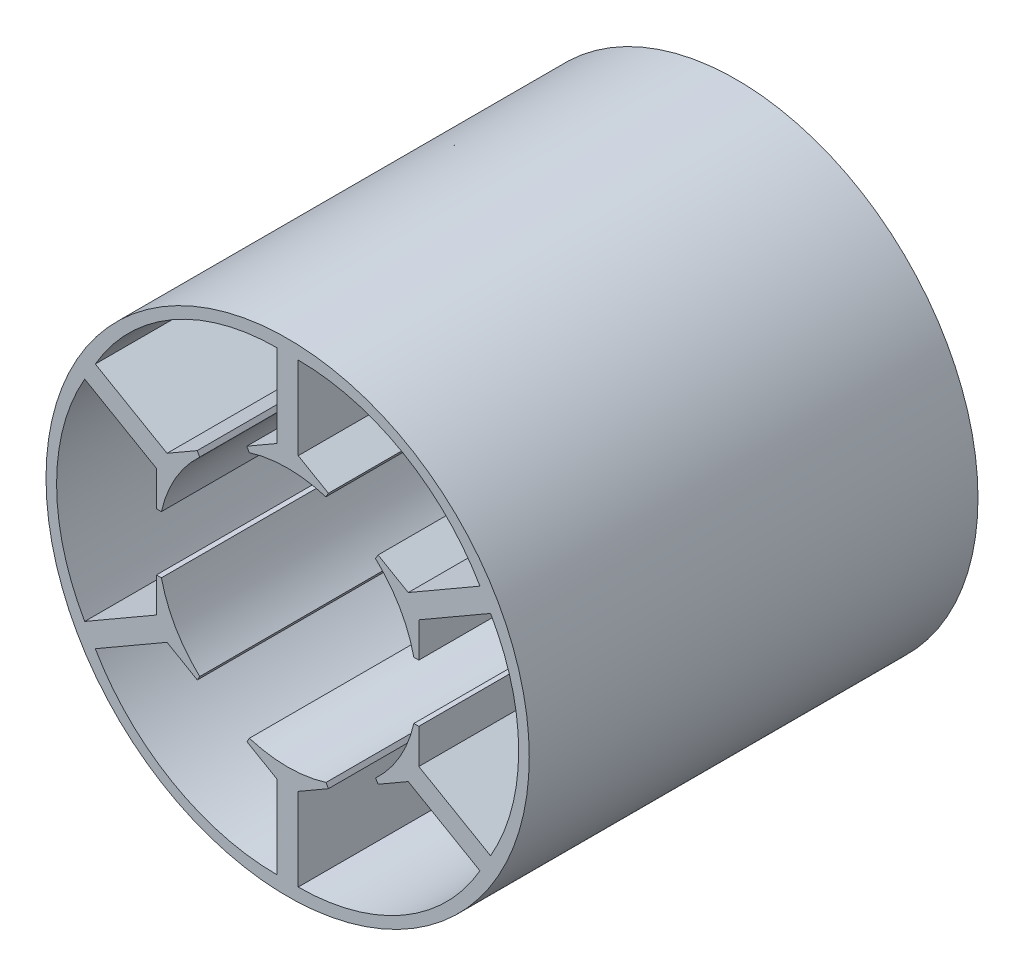
SolidWorks part; units mm, degrees
ref_plane "Front Plane" through (0, 0, 0) normal (0, 0, 1) x (1, 0, 0)
ref_plane "Top Plane" through (0, 0, 0) normal (0, 1, 0) x (1, 0, 0)
ref_plane "Right Plane" through (0, 0, 0) normal (1, 0, 0) x (0, 0, -1)
sketch "Motor_Base" plane through (0, 0, 0) normal (0, 0, 1) x (1, 0, 0)
  line L0 (0, 0) -> (0, 37.1463) construction
  line L1 (1.5331, 21.0694) -> (1.5331, 33.0694)
  line L2 (-1.5331, 21.0694) -> (-1.5331, 33.0694)
  line L3 (17.468, 11.8694) -> (27.8603, 17.8694)
  line L4 (19.0011, 9.214) -> (29.3934, 15.214)
  line L5 (19.0011, -9.186) -> (29.3934, -15.186)
  line L6 (17.468, -11.8414) -> (27.8603, -17.8414)
  line L7 (1.5331, -21.0414) -> (1.5331, -33.0414)
  line L8 (-1.5331, -21.0414) -> (-1.5331, -33.0414)
  line L9 (-17.468, -11.8414) -> (-27.8603, -17.8414)
  line L10 (-19.0011, -9.186) -> (-29.3934, -15.186)
  line L11 (-19.0011, 9.214) -> (-29.3934, 15.214)
  line L12 (-17.468, 11.8694) -> (-27.8603, 17.8694)
  line L13 (1.5331, 21.0694) -> (17.468, 11.8694)
  line L14 (-17.468, 11.8694) -> (-1.5331, 21.0694)
  line L15 (-19.0011, 9.214) -> (-19.0011, -9.186)
  line L16 (-17.468, -11.8414) -> (-1.5331, -21.0414)
  line L17 (1.5331, -21.0414) -> (17.468, -11.8414)
  line L18 (19.0011, -9.186) -> (19.0011, 9.214)
  line L20 (-9.5005, 16.4694) -> (-20.4004, 35.3485) construction
  line L23 (5.5682, 18.7398) -> (9.5005, 16.4694)
  line L25 (-15.9932, 24.7209) -> (-18.2032, 28.0912)
  line L27 (-13.4002, 26.2179) -> (-15.2139, 29.8171)
  line L28 (-15.9932, 24.7209) -> (-13.4002, 26.2179)
  line L29 (13.4123, 26.2109) -> (16.0053, 24.7139)
  line L30 (13.4123, 26.2109) -> (15.2261, 29.8101)
  line L31 (16.0053, 24.7139) -> (18.2154, 28.0842)
  line L32 (29.4055, 1.4901) -> (29.4055, -1.5041)
  line L33 (29.4055, 1.4901) -> (33.4293, 1.7189)
  line L34 (29.4055, -1.5041) -> (33.4293, -1.7329)
  line L35 (15.9932, -24.7209) -> (13.4002, -26.2179)
  line L36 (15.9932, -24.7209) -> (18.2032, -28.0912)
  line L37 (13.4002, -26.2179) -> (15.2139, -29.8171)
  line L38 (-13.4123, -26.2109) -> (-16.0053, -24.7139)
  line L39 (-13.4123, -26.2109) -> (-15.2261, -29.8101)
  line L40 (-16.0053, -24.7139) -> (-18.2154, -28.0842)
  line L41 (-29.4055, -1.4901) -> (-29.4055, 1.5041)
  line L42 (-29.4055, -1.4901) -> (-33.4293, -1.7189)
  line L43 (-29.4055, 1.5041) -> (-33.4293, 1.7329)
  line L44 (-15.9932, 24.7209) -> (-13.4002, 26.2179)
  line L45 (-13.0945, 14.3944) -> (-12.7312, 13.7651)
  line L46 (-5.9065, 18.5444) -> (-5.5432, 17.9151)
  line L47 (5.9187, 18.5374) -> (5.5553, 17.9081)
  line L49 (13.1067, 14.3874) -> (12.7434, 13.7581)
  line L50 (19.0011, 4.143) -> (18.2866, 4.143)
  line L52 (19.0011, -4.157) -> (18.2866, -4.157)
  line L53 (13.0824, -14.3734) -> (12.7312, -13.7651)
  line L55 (5.8944, -18.5234) -> (5.5432, -17.9151)
  line L56 (-5.9065, -18.5164) -> (-5.5553, -17.9081)
  line L58 (-13.0945, -14.3664) -> (-12.7434, -13.7581)
  line L59 (-19.0011, -4.143) -> (-18.2866, -4.143)
  line L61 (-19.0011, 4.157) -> (-18.2866, 4.157)
  circle A0 centre (0, 0) radius 35
  circle A4 centre (0, 0) radius 3.175
  circle A5 centre (0, 0) radius 18.75
  arc A6 (1.5331, 33.0694) -> (27.8603, 17.8694) centre (1.5331, 2.6694) cw
  circle A7 centre (0, 0) radius 4.7625
  arc A9 (29.3934, 15.214) -> (29.3934, -15.186) centre (3.0662, 0.014) cw
  arc A10 (27.8603, -17.8414) -> (1.5331, -33.0414) centre (1.5331, -2.6414) cw
  arc A11 (-1.5331, -33.0414) -> (-27.8603, -17.8414) centre (-1.5331, -2.6414) cw
  arc A12 (-29.3934, 15.214) -> (-29.3934, -15.186) centre (-3.0662, 0.014) ccw
  arc A13 (-27.8603, 17.8694) -> (-1.5331, 33.0694) centre (-1.5331, 2.6694) cw
  point P17 (0, 0)
  point P35 (0, 0.014)
  point P42 (9.5005, 16.4694)
  point P73 (0, 0)
  point P74 (-10.8113, 18.7398)
  point P99 (0, 0)
  dimension "D1" = 70
  dimension "D3" = 9.525
  dimension "D2" = 6.35
  dimension "D5" = 6
  dimension "D6" = 18.4
  dimension "D7" = 6
  dimension "D4" = 37.5
extrude "Stator_Shell" add sketch "Motor_Base" along normal blind 65 contours A0 | L18 L4 A9 L5 | A6 L3 L13 L1 | A10 L7 L17 L6 | A11 L9 L16 L8 | A12 L10 L15 L11 | A13 L2 L14 L12
extrude "Cut-Extrude1" cut sketch "Motor_Base<4>" along normal through all contours A5 A7 | A4 | A7 A4 region at (13.3758, 12.3711, 0) region at (0, 0, 0) region at (-4.6278, 0, 0)
sketch "Motor_Base<4>" plane through (0, 0, 0) normal (0, 0, 1) x (1, 0, 0) same geometry as "Motor_Base"
sketch "Stator_Lam_Support" plane through (0, 0, 0) normal (0, 0, -1) x (-1, 0, 0)
  line L0 (9.5005, 16.4694) -> (24.2852, 42.0991) construction
  line L1 (17.468, 11.8694) -> (1.5331, 21.0694) construction
  line L2 (14.3513, 31.3063) -> (13.5066, 28.0964)
  line L3 (13.5066, 28.0964) -> (17.56, 25.7582)
  line L4 (19.9157, 28.0964) -> (17.56, 25.7582)
  line L5 (34.2877, 3.2246) -> (31.0855, 2.3512)
  line L6 (34.2901, -3.1993) -> (31.0872, -2.3283)
  line L7 (31.0855, 2.3512) -> (31.0872, -2.3283)
  line L8 (19.9364, -28.0818) -> (17.579, -25.7452)
  line L9 (14.3744, -31.2957) -> (13.5273, -28.0865)
  line L10 (17.579, -25.7452) -> (13.5273, -28.0865)
  line L11 (-14.3513, -31.3063) -> (-13.5066, -28.0964)
  line L12 (-19.9157, -28.0964) -> (-17.56, -25.7582)
  line L13 (-13.5066, -28.0964) -> (-17.56, -25.7582)
  line L14 (-34.2877, -3.2246) -> (-31.0855, -2.3512)
  line L15 (-34.2901, 3.1993) -> (-31.0872, 2.3283)
  line L16 (-31.0855, -2.3512) -> (-31.0872, 2.3283)
  line L17 (-19.9364, 28.0818) -> (-17.579, 25.7452)
  line L18 (-14.3744, 31.2957) -> (-13.5273, 28.0865)
  line L19 (-17.579, 25.7452) -> (-13.5273, 28.0865)
  arc A0 (14.3513, 31.3063) -> (19.9157, 28.0964) centre (0, 0) cw
  arc A2 (34.2877, 3.2246) -> (34.2901, -3.1993) centre (0, 0) cw
  arc A3 (19.9364, -28.0818) -> (14.3744, -31.2957) centre (0, 0) cw
  arc A4 (-14.3513, -31.3063) -> (-19.9157, -28.0964) centre (0, 0) cw
  arc A5 (-34.2877, -3.2246) -> (-34.2901, 3.1993) centre (0, 0) cw
  arc A6 (-19.9364, 28.0818) -> (-14.3744, 31.2957) centre (0, 0) cw
  point P8 (1.5331, 33.0694)
  point P11 (15.5333, 26.9273)
  point P35 (0, 0)
  point P36 (0, 0)
extrude "Stator Lamination Support" add sketch "Stator_Lam_Support" against normal blind 17.35
sketch "Sketch6" plane through (0, 0, 65) normal (0, 0, 1) x (1, 0, 0)
  line L0 (9.5005, 16.4694) -> (18.75, 32.5036) construction
  line L1 (1.5331, 21.0694) -> (17.468, 11.8694) construction
  line L2 (14.4053, 16.6666) -> (11.564, 11.7412)
  line L3 (7.2157, 20.8139) -> (14.4053, 16.6666)
  line L4 (11.564, 11.7412) -> (4.3745, 15.8885)
  line L5 (4.3745, 15.8885) -> (7.2157, 20.8139)
  line L6 (21.6333, 4.158) -> (21.6363, -4.142)
  line L7 (15.9471, 4.1559) -> (21.6333, 4.158)
  line L8 (21.6363, -4.142) -> (15.9502, -4.1441)
  line L9 (15.9502, -4.1441) -> (15.9471, 4.1559)
  line L10 (14.4175, -16.656) -> (7.2311, -20.8086)
  line L11 (11.5727, -11.7327) -> (14.4175, -16.656)
  line L12 (7.2311, -20.8086) -> (4.3862, -15.8853)
  line L13 (4.3862, -15.8853) -> (11.5727, -11.7327)
  line L14 (-7.2157, -20.8139) -> (-14.4053, -16.6666)
  line L15 (-4.3745, -15.8885) -> (-7.2157, -20.8139)
  line L16 (-14.4053, -16.6666) -> (-11.564, -11.7412)
  line L17 (-11.564, -11.7412) -> (-4.3745, -15.8885)
  line L18 (-21.6333, -4.158) -> (-21.6363, 4.142)
  line L19 (-15.9471, -4.1559) -> (-21.6333, -4.158)
  line L20 (-21.6363, 4.142) -> (-15.9502, 4.1441)
  line L21 (-15.9502, 4.1441) -> (-15.9471, -4.1559)
  line L22 (-14.4175, 16.656) -> (-7.2311, 20.8086)
  line L23 (-11.5727, 11.7327) -> (-14.4175, 16.656)
  line L24 (-7.2311, 20.8086) -> (-4.3862, 15.8853)
  line L25 (-4.3862, 15.8853) -> (-11.5727, 11.7327)
  point P7 (10.8105, 18.7403)
  point P32 (0, 0)
  dimension "D1" = 4.15
extrude "Cut-Extrude3" cut sketch "Sketch6" against normal through all
